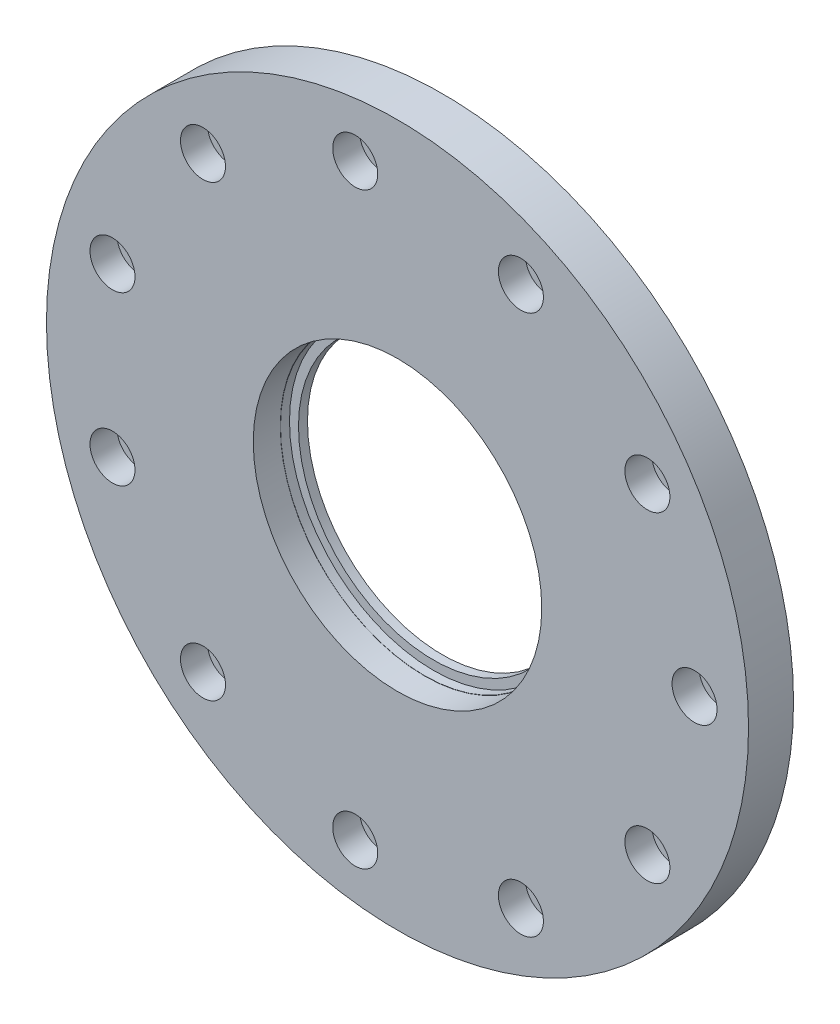
SolidWorks part; units mm, degrees
ref_plane "Front Plane" through (0, 0, 0) normal (0, 0, 1) x (1, 0, 0)
ref_plane "Top Plane" through (0, 0, 0) normal (0, 1, 0) x (1, 0, 0)
ref_plane "Right Plane" through (0, 0, 0) normal (1, 0, 0) x (0, 0, -1)
sketch "Sketch1" plane through (0, 0, 0) normal (0, 0, 1) x (1, 0, 0)
  circle A0 centre (0, 0) radius 39
  circle A1 centre (0, 0) radius 33 construction
  circle A2 centre (33, 0) radius 2.5
  circle A3 centre (27.7614, -17.8411) radius 2.5
  circle A4 centre (13.7087, -30.0179) radius 2.5
  circle A5 centre (-4.6964, -32.6641) radius 2.5
  circle A6 centre (-21.6104, -24.9397) radius 2.5
  circle A7 centre (-31.6633, -9.2972) radius 2.5
  circle A8 centre (-31.6633, 9.2972) radius 2.5
  circle A9 centre (-21.6104, 24.9397) radius 2.5
  circle A10 centre (-4.6964, 32.6641) radius 2.5
  circle A11 centre (13.7087, 30.0179) radius 2.5
  circle A12 centre (27.7614, 17.8411) radius 2.5
  circle A13 centre (0, 0) radius 16.025
  point P28 (0, 0)
extrude "Boss-Extrude1" add sketch "Sketch1" along normal blind 3
sketch "Sketch2" plane through (0, 0, 0) normal (0, 0, -1) x (-1, 0, 0)
  circle A0 centre (0, 0) radius 16
  circle A1 centre (0, 0) radius 39
  dimension "D1" = 32
extrude "Boss-Extrude2" add sketch "Sketch2" along normal blind 2 contours A1 | A0
sketch "Sketch3" plane through (0, 0, 3) normal (0, 0, 1) x (1, 0, 0)
  circle A0 centre (33, 0) radius 1.6
  circle A1 centre (27.7614, -17.8411) radius 1.6
  circle A2 centre (13.7087, -30.0179) radius 1.6
  circle A3 centre (-4.6964, -32.6641) radius 1.6
  circle A4 centre (-21.6104, -24.9397) radius 1.6
  circle A5 centre (-31.6633, -9.2972) radius 1.6
  circle A6 centre (-31.6633, 9.2972) radius 1.6
  circle A7 centre (-21.6104, 24.9397) radius 1.6
  circle A8 centre (-4.6964, 32.6641) radius 1.6
  circle A9 centre (13.7087, 30.0179) radius 1.6
  circle A10 centre (27.7614, 17.8411) radius 1.6
  point P25 (0, 0)
  dimension "D1" = 3.2
  dimension "D2" = 11
extrude "Cut-Extrude1" cut sketch "Sketch3" against normal through all
sketch "Sketch4" plane through (0, 0, -2) normal (0, 0, -1) x (-1, 0, 0)
  circle A0 centre (0, 0) radius 16
  circle A1 centre (0, 0) radius 15
  dimension "D1" = 32
  dimension "D2" = 30
extrude "Boss-Extrude3" add sketch "Sketch4" against normal blind 1
